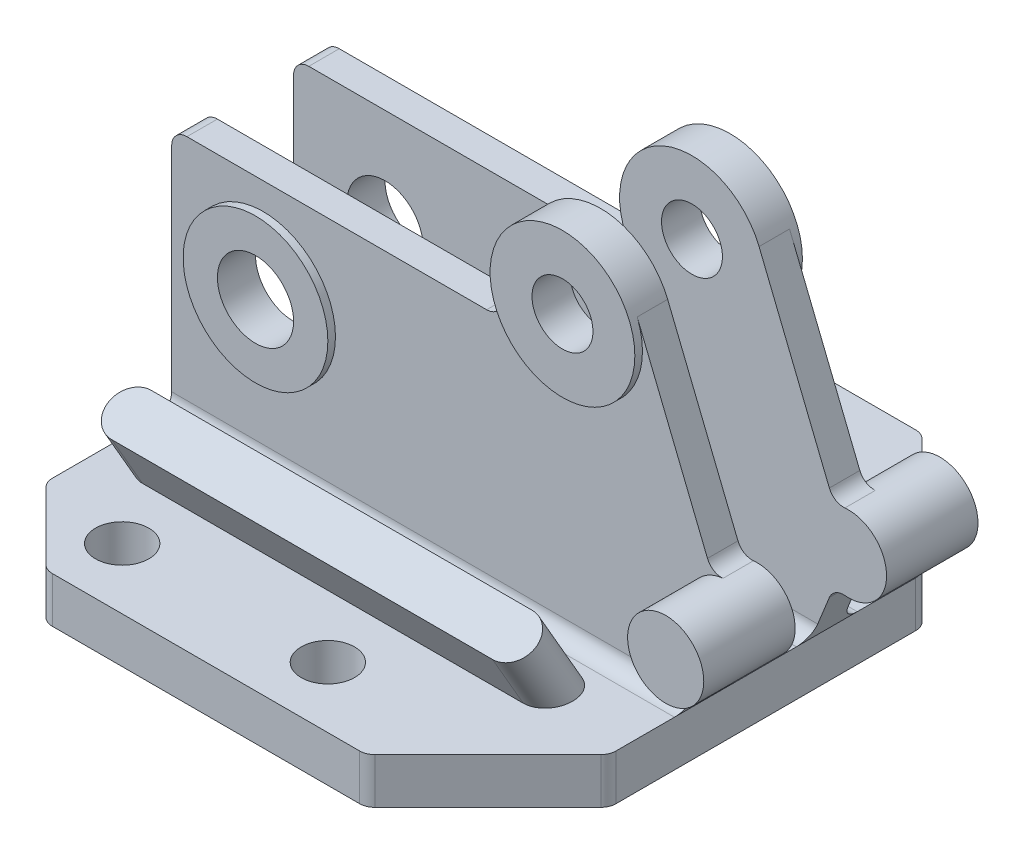
SolidWorks part; units mm, degrees
material "Copper"
ref_plane "Front Plane" through (0, 0, 0) normal (0, 0, 1) x (1, 0, 0)
ref_plane "Top Plane" through (0, 0, 0) normal (0, 1, 0) x (1, 0, 0)
ref_plane "Right Plane" through (0, 0, 0) normal (1, 0, 0) x (0, 0, -1)
sketch "Sketch1" plane through (0, 0, 0) normal (0, 1, 0) x (1, 0, 0)
  line L0 (0, 0) -> (68, 0)
  line L1 (68, 0) -> (68, 36.5)
  line L2 (68, 36.5) -> (0, 36.5)
  line L3 (0, 36.5) -> (0, 0)
  line L4 (-13.2098, 0) -> (79.1172, 0) construction
  dimension "D1" = 68
  dimension "D2" = 73
extrude "Boss-Extrude1" add sketch "Sketch1" along normal blind 6
sketch "Sketch2" plane through (0, 6, 0) normal (0, 1, 0) x (1, 0, 0)
  line L0 (68, 36.5) -> (0, 36.5) construction
  line L1 (0, 36.5) -> (0, 0) construction
  circle A0 centre (12, 28.5) radius 3.5
  circle A1 centre (39, 28.5) radius 3.5
  dimension "D4" = 7
  dimension "D1" = 27
  dimension "D2" = 8
  dimension "D3" = 12
extrude "Cut-Extrude1" cut sketch "Sketch2" against normal through all
sketch "Sketch3" plane through (0, 6, 0) normal (0, 1, 0) x (1, 0, 0)
  line L0 (-7.5154, 0) -> (70.6104, 0) construction
  line L1 (0, 10) -> (68, 10)
  line L2 (0, 10) -> (0, 6)
  line L3 (0, 6) -> (68, 6)
  line L4 (68, 10) -> (68, 6)
  line L5 (0, 36.5) -> (0, 0) construction
  line L6 (68, 0) -> (68, 36.5) construction
  dimension "D1" = 12
  dimension "D2" = 20
extrude "Boss-Extrude2" add sketch "Sketch3" along normal blind 1
sketch "Sketch4" plane through (0, 0, -6) normal (0, 0, 1) x (1, 0, 0)
  line L0 (68, 6) -> (72.8483, 18)
  line L1 (72.8483, 18) -> (61.1078, 47.0588)
  line L2 (44.5536, 38) -> (0, 38)
  line L3 (0, 38) -> (0, 6)
  line L4 (0, 6) -> (68, 6)
  line L5 (60, -14.6904) -> (60, 84.1107) construction
  arc A0 (61.1078, 47.0588) -> (44.5536, 38) centre (52.2996, 43.5) ccw
  circle A1 centre (12, 25) radius 5
  circle A2 centre (52.2996, 43.5) radius 4
  dimension "D1" = 10
  dimension "D8" = 9.5
  dimension "D9" = 8
  dimension "D2" = 32
  dimension "D3" = 19
  dimension "D4" = 12
  dimension "D5" = 22
  dimension "D6" = 37.5
  dimension "D7" = 22
  dimension "D10" = 12
extrude "Boss-Extrude3" add sketch "Sketch4" against normal up to surface (4 mm away) up to face at (34, 6.5, -10)
mirror "Mirror1" about plane through (0, 0, 0) normal (0, 0, 1) of "Boss-Extrude1", "Cut-Extrude1", "Boss-Extrude2", "Boss-Extrude3"
fillet "Fillet1" radius 2 4 edges at (34, 6, -10) (34, 6, -6) (34, 6, 10) (34, 6, 6)
sketch "Sketch5" plane through (0, 0, 10) normal (0, 0, 1) x (1, 0, 0)
  circle A0 centre (52.2996, 43.5) radius 4 construction
  circle A1 centre (52.2996, 43.5) radius 4
  circle A2 centre (52.2996, 43.5) radius 9.5
  circle A3 centre (12, 25) radius 5 construction
  circle A4 centre (12, 25) radius 5
  circle A5 centre (12, 25) radius 9.5
  arc A6 (61.1078, 47.0588) -> (44.5536, 38) centre (52.2996, 43.5) ccw construction
  dimension "D1" = 19
extrude "Boss-Extrude4" add sketch "Sketch5" along normal blind 1
fillet "Fillet2" radius 2 4 edges at (44.5536, 38, 8) (44.5536, 38, -8) (0, 38, -8) (0, 38, 8)
chamfer "Chamfer1" distance 10 angle 45 2 edges at (0, 3, 36.5) (0, 3, -36.5)
chamfer "Chamfer2" distance 16 angle 45 2 edges at (68, 3, 36.5) (68, 3, -36.5)
fillet "Fillet3" radius 2 8 edges at (52, 3, -36.5) (68, 3, -20.5) (68, 3, 20.5) (52, 3, 36.5) (10, 3, 36.5) (0, 3, 26.5) (0, 3, -26.5) (10, 3, -36.5)
mirror "Mirror2" about plane through (0, 0, 0) normal (0, 0, 1) of "Boss-Extrude4"
sketch "Sketch7" plane through (0, 0, 0) normal (0, 0, 1) x (1, 0, 0)
  circle A0 centre (72.8483, 18) radius 5
  dimension "D1" = 10
extrude "Boss-Extrude6" add sketch "Sketch7" along normal mid plane 36
sketch "Sketch8" plane through (0, 0, 6) normal (0, 0, -1) x (-1, 0, 0)
  line L0 (0, 36) -> (0, 8) construction
  line L1 (-57.6304, 35) -> (-82.6304, 35)
  line L2 (-57.6304, 35) -> (-57.6304, 10)
  line L3 (-57.6304, 10) -> (-82.6304, 10)
  line L4 (-82.6304, 35) -> (-82.6304, 10)
  dimension "D1" = 25
  dimension "D2" = 25
  dimension "D3" = 10
  dimension "D4" = 82.6304
extrude "Cut-Extrude2" cut sketch "Sketch8" along normal up to surface (12 mm away) up to face at (39.164, 28.911, -6)
fillet "Fillet8" radius 2 4 edges at (70.9753, 13.3641, -8) (70.9753, 22.6359, -8) (70.9753, 22.6359, 8) (70.9753, 13.3641, 8)
ref_plane "Plane2" through (0, 20.305, 11.7231) normal (0, 0.866, 0.5) x (-1, 0, 0)
sketch "Sketch11" plane through (0, 20.305, 11.7231) normal (0, 0.866, 0.5) x (-1, 0, 0)
  line L0 (-6.5, 11.6099) -> (-56.5, 11.6099) construction
  line L1 (-6.5, 8.6099) -> (-56.5, 8.6099)
  line L2 (-6.5, 14.6099) -> (-56.5, 14.6099)
  line L3 (0, 7.3923) -> (0, 19.2322) construction
  line L4 (-51.1716, 28.6099) -> (-10.8284, 28.6099) construction
  arc A0 (-6.5, 8.6099) -> (-6.5, 14.6099) centre (-6.5, 11.6099) ccw
  arc A1 (-56.5, 14.6099) -> (-56.5, 8.6099) centre (-56.5, 11.6099) ccw
  point P2 (-31.5, 11.6099)
  dimension "D1" = 50
  dimension "D2" = 6
  dimension "D3" = 6.5
  dimension "D4" = 17
extrude "Boss-Extrude8" add sketch "Sketch11" against normal up to surface (11.547 mm away) up to face at (32.8, 6, -26.2741)
equation "\"A\"= 68"
equation "\"B\"= 73"
equation "\"C\"= 12"
equation "\"D1@Sketch1\"=\"A\""
equation "\"D2@Sketch1\"=\"B\""
equation "\"D1@Sketch3\"=\"C\""
